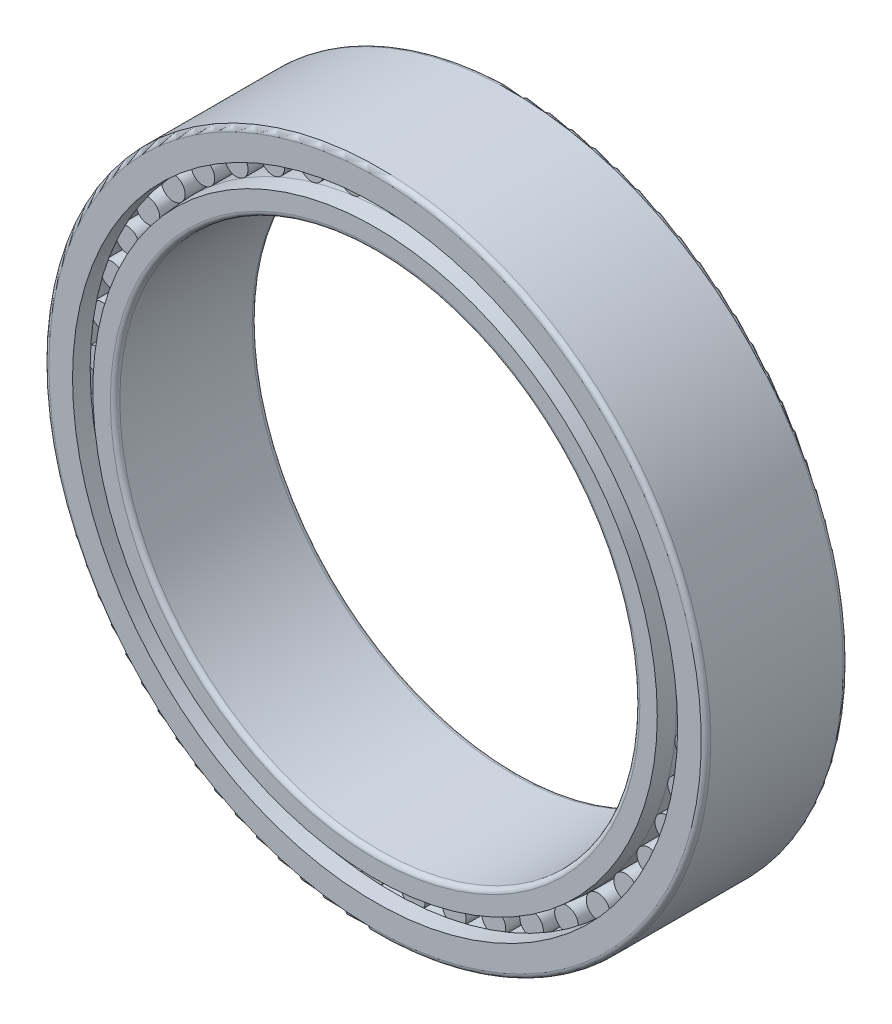
SolidWorks part; units mm, degrees
ref_plane "Front Plane" through (0, 0, 0) normal (0, 0, 1) x (1, 0, 0)
ref_plane "Top Plane" through (0, 0, 0) normal (0, 1, 0) x (1, 0, 0)
ref_plane "Right Plane" through (0, 0, 0) normal (1, 0, 0) x (0, 0, -1)
sketch "BaseSke" plane through (0, 0, 0) normal (1, 0, 0) x (0, 0, -1)
  line L0 (-47.2296, 0) -> (24.6132, 0) construction
  line L1 (-47.2296, 62.5) -> (24.6132, 62.5) construction
  line L2 (0, 129.5214) -> (0, -86.3012) construction
  line L3 (-11.25, 62.5) -> (-11.25, 65) construction
  line L4 (-15, 70) -> (15, 70) construction
  line L5 (-15, 55) -> (15, 55) construction
  line L6 (-11.25, 60) -> (11.25, 60)
  line L7 (-11.25, 60) -> (-11.25, 62.5)
  line L8 (-11.25, 62.5) -> (11.25, 62.5)
  line L9 (11.25, 60) -> (11.25, 62.5)
  line L10 (-11.25, 65) -> (11.25, 65) construction
  line L11 (11.25, 65) -> (11.25, 62.5) construction
  dimension "D2" = 22.5
  dimension "D1" = 125
revolve "Roller" add sketch "BaseSke" angle 360 about L8
sketch "OuterRaceSke" plane through (0, 0, 0) normal (1, 0, 0) x (0, 0, -1)
  line L0 (0, 0) -> (0, 87.5396) construction
  line L1 (-15, 70) -> (15, 70)
  line L2 (-15, 70) -> (-15, 64)
  line L3 (-15, 64) -> (-11.275, 64)
  line L4 (15, 70) -> (15, 64)
  line L5 (-50.3916, 0) -> (55.2197, 0) construction
  line L6 (-11.25, 65) -> (11.25, 65) construction
  line L7 (11.275, 64) -> (15, 64)
  line L9 (-11.275, 64) -> (-11.275, 64.98)
  line L10 (-11.275, 64.98) -> (11.275, 64.98)
  line L11 (11.275, 64) -> (11.275, 64.98)
  dimension "D2" = 128
  dimension "D1" = 22.55
  dimension "D3" = 0.02
revolve "OuterRace" add sketch "OuterRaceSke" angle 360 about L5
sketch "InnerRaceSke" plane through (0, 0, 0) normal (1, 0, 0) x (0, 0, -1)
  line L0 (-70.8626, 0) -> (113.5527, 0) construction
  line L1 (0, 58.441) -> (0, -70.8113) construction
  line L2 (-15, 55) -> (15, 55)
  line L3 (-15, 55) -> (-15, 59.6941)
  line L5 (-11.275, 60.02) -> (-15, 59.6941)
  line L6 (0, 129.5214) -> (0, -86.3012) construction
  line L7 (-11.275, 60.02) -> (11.275, 60.02)
  line L9 (15, 55) -> (15, 59.6941)
  line L10 (11.275, 60.02) -> (15, 59.6941)
  line L13 (-11.25, 60) -> (11.25, 60) construction
  point P17 (0, 55)
  dimension "D1" = 22.55
  dimension "D2" = 0.02
  dimension "D3" = 5
revolve "InnerRace" add sketch "InnerRaceSke" angle 360 about L0
fillet "Fillet1" radius 1 4 edges at (55, 0, 15) (70, 0, -15) (70, 0, 15) (55, 0, -15)
pattern_circular "CirPatternBall" count 45 over 360 about axis through (0, 0, 50.3916) along (0, 0, -1) of "Roller"
sketch "SimplifiedSke" plane through (0, 0, 0) normal (1, 0, 0) x (0, 0, -1)
  line L0 (37.5911, 0) -> (-37.5911, 0) construction
  line L1 (-13.1351, 62.5) -> (13.151, 62.5) construction
  line L2 (-11.25, 65) -> (11.25, 65)
  line L3 (-11.25, 65) -> (-11.25, 60)
  line L4 (-11.25, 60) -> (11.25, 60)
  line L5 (11.25, 65) -> (11.25, 60)
  line L6 (-47.2296, 62.5) -> (24.6132, 62.5) construction
revolve "Simplified" [suppressed] add sketch "SimplifiedSke" angle 360 about L0
equation "\"D2@BaseSke\" = \"Bearing_Thickness@BaseSke\"*0.75"
equation "\"D1@BaseSke\" =  ( \"Bearing_Outside_Diameter@BaseSke\" + \"Bearing_Inside_Diameter@BaseSke\" )  / 2"
equation "\"D1@OuterRaceSke\" = \"Bearing_Thickness@BaseSke\"*0.75+0.05"
equation "\"D2@OuterRaceSke\" =\"Bearing_Outside_Diameter@BaseSke\" -  ( \"Bearing_Outside_Diameter@BaseSke\" - \"Bearing_Inside_Diameter@BaseSke\"  )/ 2.5 "
equation "\"D1@InnerRaceSke\" = \"Bearing_Thickness@BaseSke\"*0.75+0.05"
equation "\"D1@CirPatternBall\" =  int(  ( \"Bearing_Outside_Diameter@BaseSke\" + \"Bearing_Inside_Diameter@BaseSke\" )  / 2 *  pi  /  ( \"Bearing_Outside_Diameter@BaseSke\" - \"Bearing_Inside_Diameter@BaseSke\" ) * 3.5 ) "
